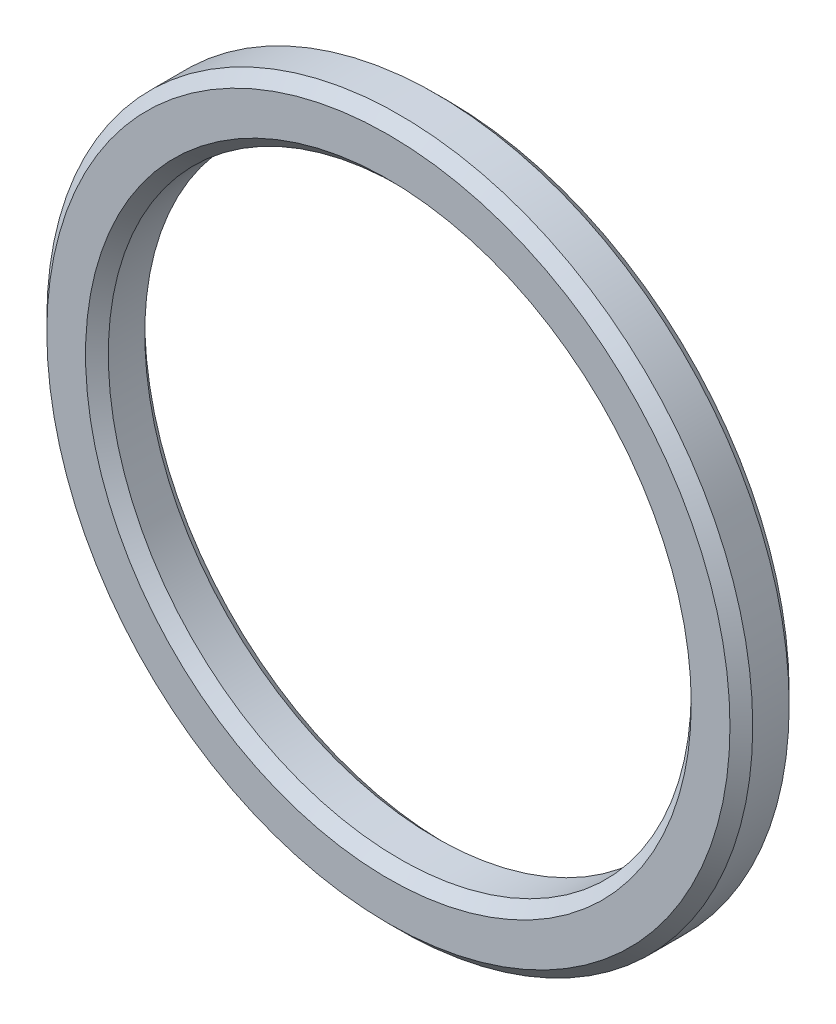
SolidWorks part; units mm, degrees
ref_plane "Front Plane" through (0, 0, 0) normal (0, 0, 1) x (1, 0, 0)
ref_plane "Top Plane" through (0, 0, 0) normal (0, 1, 0) x (1, 0, 0)
ref_plane "Right Plane" through (0, 0, 0) normal (1, 0, 0) x (0, 0, -1)
sketch "Sketch1" plane through (0, 0, 0) normal (0, 0, 1) x (1, 0, 0)
  circle A0 centre (0, 0) radius 12.8
  circle A1 centre (0, 0) radius 15.5
  dimension "D1" = 25.6
  dimension "D2" = 31
extrude "Boss-Extrude1" add sketch "Sketch1" along normal blind 2.6
chamfer "Chamfer1" distance 0.5 angle 45 4 edges at (12.8, 0, 0) (15.5, 0, 0) (12.8, 0, 2.6) (15.5, 0, 2.6)
